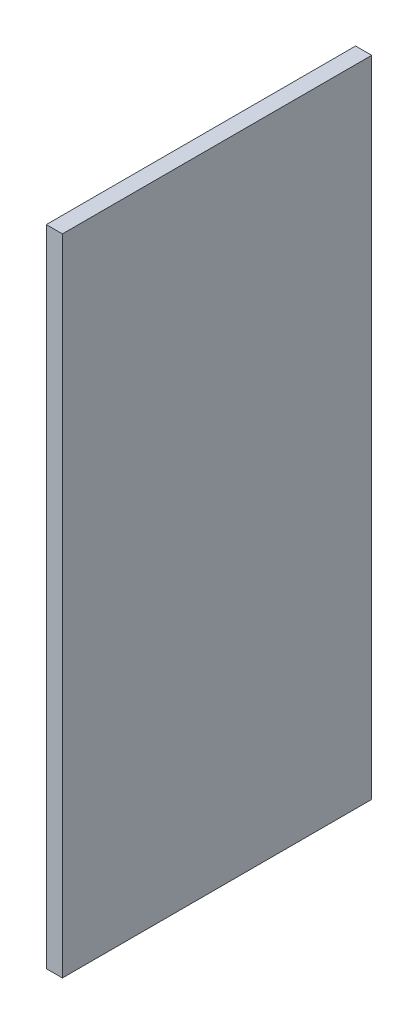
SolidWorks part; units mm, degrees
ref_plane "Front Plane" through (0, 0, 0) normal (0, 0, 1) x (1, 0, 0)
ref_plane "Top Plane" through (0, 0, 0) normal (0, 1, 0) x (1, 0, 0)
ref_plane "Right Plane" through (0, 0, 0) normal (1, 0, 0) x (0, 0, -1)
sketch "Sketch1" plane through (0, 0, 0) normal (1, 0, 0) x (0, 0, -1)
  line L1 (0, 0) -> (60.96, 0)
  line L2 (0, 0) -> (0, 127)
  line L3 (0, 127) -> (60.96, 127)
  line L4 (60.96, 0) -> (60.96, 127)
  dimension "D1" = 60.96
  dimension "D2" = 127
extrude "Boss-Extrude1" add sketch "Sketch1" along normal blind 3.175 contours L2 L3 L4 L1
